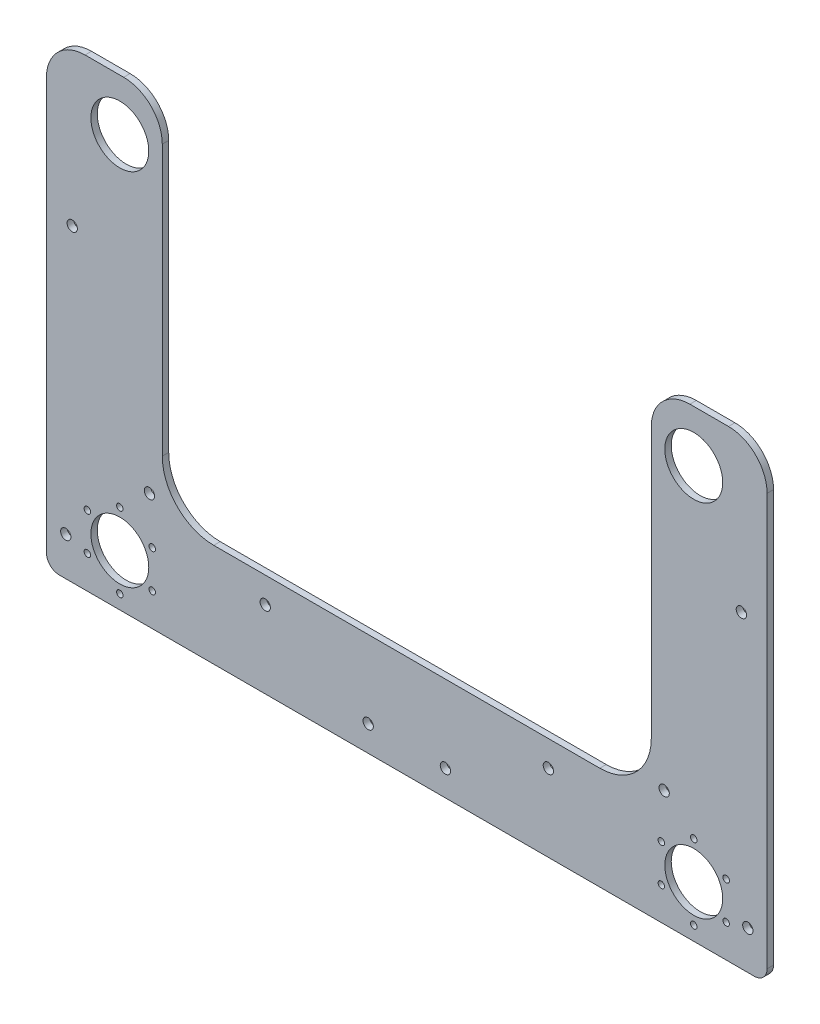
SolidWorks part; units mm, degrees
ref_plane "Front Plane" through (0, 0, 0) normal (0, 0, 1) x (1, 0, 0)
ref_plane "Top Plane" through (0, 0, 0) normal (0, 1, 0) x (1, 0, 0)
ref_plane "Right Plane" through (0, 0, 0) normal (1, 0, 0) x (0, 0, -1)
sketch "Sketch1" plane through (0, 0, 0) normal (0, 0, 1) x (1, 0, 0)
  line L5 (120.65, -152.4) -> (120.65, -6.35)
  line L6 (127, 0) -> (171.45, 0) construction
  line L7 (177.8, -6.35) -> (177.8, -222.25)
  line L10 (0, -206.2199) -> (0, -63.6275) construction
  line L11 (-54.9244, 0) -> (300.6756, 0) construction
  line L13 (12.7, -177.8) -> (95.25, -177.8)
  line L14 (12.7, -228.6) -> (171.45, -228.6)
  line L15 (141.605, -25.4) -> (141.605, -84.2822) construction
  line L16 (141.605, -25.4) -> (141.605, -127) construction
  line L17 (-141.605, -25.4) -> (-141.605, -203.2) construction
  line L18 (-141.605, -25.4) -> (-141.605, -127) construction
  line L19 (-141.605, -19.05) -> (-141.605, -77.9322) construction
  line L20 (141.605, -25.4) -> (141.605, -203.2) construction
  line L22 (-120.65, -152.4) -> (-120.65, -6.35)
  line L23 (-12.7, -177.8) -> (-95.25, -177.8)
  line L24 (-12.7, -228.6) -> (-171.45, -228.6)
  line L25 (-177.8, -6.35) -> (-177.8, -222.25)
  line L26 (-12.7, -177.8) -> (12.7, -177.8)
  line L27 (-12.7, -228.6) -> (12.7, -228.6)
  line L28 (-177.8, -6.35) -> (-177.8, 6.35)
  line L29 (-165.1, 19.05) -> (-133.35, 19.05)
  line L30 (-120.65, 6.35) -> (-120.65, -6.35)
  line L31 (120.65, 6.35) -> (120.65, -6.35)
  line L32 (177.8, -6.35) -> (177.8, 6.35)
  line L33 (165.1, 19.05) -> (133.35, 19.05)
  arc A0 (95.25, -177.8) -> (120.65, -152.4) centre (95.25, -152.4) ccw
  arc A4 (120.65, -6.35) -> (127, 0) centre (127, -6.35) cw construction
  circle A8 centre (141.605, -25.4) radius 14.2875
  circle A9 centre (141.605, -25.4) radius 38.1 construction
  arc A10 (177.8, -6.35) -> (171.45, 0) centre (171.45, -6.35) ccw construction
  arc A11 (171.45, -228.6) -> (177.8, -222.25) centre (171.45, -222.25) ccw
  arc A14 (141.605, -82.55) -> (120.9214, -78.6758) centre (141.605, -25.4) ccw construction
  arc A15 (-141.605, -82.55) -> (-120.9214, -78.6758) centre (-141.605, -25.4) cw construction
  circle A16 centre (-141.605, -25.4) radius 38.1 construction
  circle A17 centre (-141.605, -25.4) radius 14.2875
  arc A19 (-95.25, -177.8) -> (-120.65, -152.4) centre (-95.25, -152.4) cw
  circle A20 centre (141.605, -127) radius 38.1 construction
  circle A21 centre (-141.605, -127) radius 38.1 construction
  arc A23 (-171.45, -228.6) -> (-177.8, -222.25) centre (-171.45, -222.25) cw
  circle A24 centre (-141.605, -203.2) radius 14.2875
  circle A25 centre (-141.605, -184.7225) radius 1.6002
  circle A26 centre (-125.603, -193.9612) radius 1.6002
  circle A27 centre (-125.603, -212.4388) radius 1.6002
  circle A28 centre (-141.605, -221.6775) radius 1.6002
  circle A29 centre (-157.607, -212.4388) radius 1.6002
  circle A30 centre (-157.607, -193.9612) radius 1.6002
  circle A31 centre (157.607, -212.4388) radius 1.6002
  circle A32 centre (157.607, -193.9612) radius 1.6002
  circle A33 centre (141.605, -184.7225) radius 1.6002
  circle A34 centre (125.603, -193.9612) radius 1.6002
  circle A35 centre (125.603, -212.4388) radius 1.6002
  circle A36 centre (141.605, -221.6775) radius 1.6002
  circle A37 centre (141.605, -203.2) radius 14.2875
  circle A39 centre (-69.85, -190.5) radius 2.54
  circle A40 centre (69.85, -190.5) radius 2.54
  circle A42 centre (-19.05, -215.9) radius 2.54
  circle A43 centre (-127, -171.45) radius 2.54
  arc A44 (-133.35, 19.05) -> (-120.65, 6.35) centre (-133.35, 6.35) cw
  arc A45 (-177.8, 6.35) -> (-165.1, 19.05) centre (-165.1, 6.35) cw
  arc A46 (133.35, 19.05) -> (120.65, 6.35) centre (133.35, 6.35) ccw
  arc A47 (177.8, 6.35) -> (165.1, 19.05) centre (165.1, 6.35) ccw
  circle A50 centre (-149.225, 6.35) radius 2.54
  circle A51 centre (127, -171.45) radius 2.54
  circle A53 centre (149.225, 6.35) radius 2.54
  circle A54 centre (-168.275, -209.55) radius 2.54
  circle A56 centre (168.275, -209.55) radius 2.54
  circle A58 centre (-165.1, -76.2) radius 2.54
  circle A59 centre (165.1, -76.2) radius 2.54
  circle A60 centre (19.05, -215.9) radius 2.54
  point P2 (177.8, -44.45)
  point P18 (177.8, 0)
  point P23 (177.8, -228.6)
  point P24 (177.8, -228.6)
  point P31 (177.8, 0)
  point P48 (-177.8, 0)
  point P49 (-177.8, -228.6)
  point P51 (-177.8, -44.45)
  point P78 (-141.605, -203.2)
  dimension "D6" = 25.4
  dimension "D7" = 6.35
  dimension "D8" = 6.35
  dimension "D9" = 177.8
  dimension "D10" = 28.575
  dimension "D12" = 76.2
  dimension "D13" = 57.15
  dimension "D15" = 28.575
  dimension "D18" = 76.2
  dimension "D21" = 3.2004
  dimension "D29" = 9.525
  dimension "D32" = 5.08
  dimension "D35" = 5.08
  dimension "D37" = 5.08
  dimension "D40" = 12.7
  dimension "D43" = 5.08
  dimension "D45" = 12.7
  dimension "D30" = 5.08
  dimension "D41" = 5.08
  dimension "D2" = 120.65
  dimension "D3" = 177.8
  dimension "D4" = 228.6
  dimension "D5" = 177.8
  dimension "D11" = 20.955
  dimension "`" = 25.4
  dimension "D14" = 57.15
  dimension "D16" = 184.15
  dimension "D17" = 101.6
  dimension "D19" = 25.4
  dimension "D20" = 107.95
  dimension "D22" = 0
  dimension "D23" = 18.4775
  dimension "D25" = 6.9225
  dimension "D26" = 19.05
  dimension "D27" = 25.4
  dimension "D28" = 25.4
  dimension "D31" = 95.25
  dimension "D33" = 12.7
  dimension "D34" = 38.1
  dimension "D36" = 12.7
  dimension "D38" = 57.15
  dimension "D39" = 19.05
  dimension "D42" = 6.35
  dimension "D44" = 28.575
  dimension "D46" = 19.05
  dimension "D24" = 6
extrude "Boss-Extrude3" add sketch "Sketch1" along normal blind 3.175
sketch "Sketch2" plane through (0, 0, 3.175) normal (0, 0, 1) x (1, 0, 0)
  line L0 (-133.35, 19.05) -> (-165.1, 19.05) construction
  line L1 (-177.8, 19.05) -> (177.8, 19.05)
  line L2 (-177.8, 19.05) -> (-177.8, 0)
  line L3 (-177.8, 0) -> (177.8, 0)
  line L4 (177.8, 19.05) -> (177.8, 0)
  line L5 (-177.8, 6.35) -> (-177.8, -222.25) construction
  line L6 (177.8, -222.25) -> (177.8, 6.35) construction
  dimension "D1" = 19.05
extrude "Cut-Extrude1" cut sketch "Sketch2" against normal through all
fillet "Fillet1" radius 19.05 4 edges at (177.8, 0, 1.5875) (120.65, 0, 1.5875) (-120.65, 0, 1.5875) (-177.8, 0, 1.5875)
